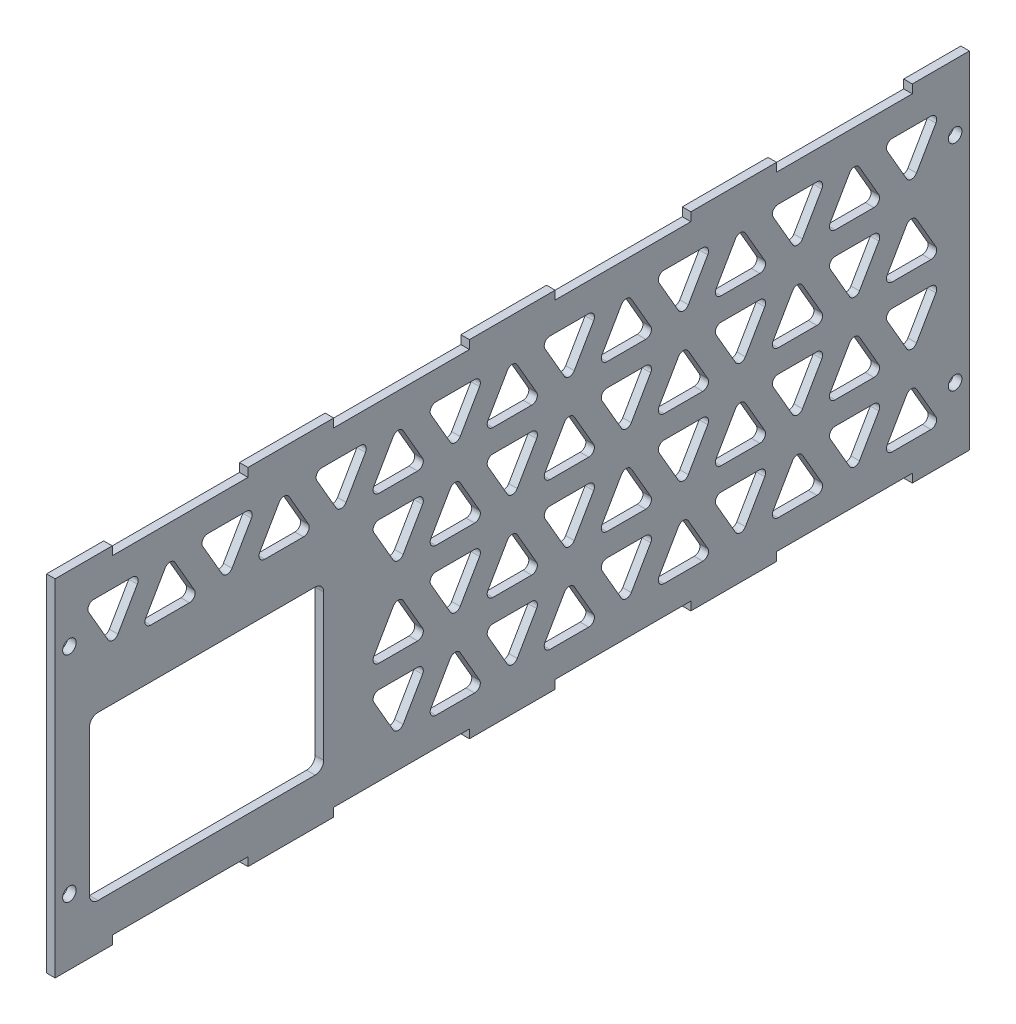
SolidWorks part; units mm, degrees
ref_plane "Front Plane" through (0, 0, 0) normal (0, 0, 1) x (1, 0, 0)
ref_plane "Top Plane" through (0, 0, 0) normal (0, 1, 0) x (1, 0, 0)
ref_plane "Right Plane" through (0, 0, 0) normal (1, 0, 0) x (0, 0, -1)
sketch "Sketch1" plane through (0, 0, 0) normal (1, 0, 0) x (0, 0, -1)
  line L1 (-160, -57.5) -> (160, -57.5)
  line L2 (-160, -57.5) -> (-160, 57.5)
  line L3 (-160, 57.5) -> (160, 57.5)
  line L4 (160, -57.5) -> (160, 57.5)
  line L5 (-160, -57.5) -> (160, 57.5) construction
  line L6 (-160, 57.5) -> (160, -57.5) construction
  point P0 (0, 0)
  dimension "D1" = 320
  dimension "D2" = 115
extrude "Boss-Extrude1" add sketch "Sketch1" along normal mid plane 3
sketch "Sketch2" plane through (1.5, 0, 0) normal (1, 0, 0) x (0, 0, -1)
  line L0 (160, 57.5) -> (-160, 57.5) construction
  line L1 (-160, 57.5) -> (-140, 57.5)
  line L2 (-160, 57.5) -> (-160, 60.5)
  line L3 (-160, 60.5) -> (-140, 60.5)
  line L4 (-140, 57.5) -> (-140, 60.5)
  line L5 (-92.5, 57.5) -> (-62.5, 57.5)
  line L6 (-92.5, 57.5) -> (-92.5, 60.5)
  line L7 (-92.5, 60.5) -> (-62.5, 60.5)
  line L8 (-62.5, 57.5) -> (-62.5, 60.5)
  line L9 (-15, 57.5) -> (-15, 60.5)
  line L10 (-15, 57.5) -> (15, 57.5)
  line L11 (15, 57.5) -> (15, 60.5)
  line L12 (-15, 60.5) -> (15, 60.5)
  line L13 (62.5, 57.5) -> (62.5, 60.5)
  line L14 (62.5, 57.5) -> (92.5, 57.5)
  line L15 (92.5, 57.5) -> (92.5, 60.5)
  line L16 (62.5, 60.5) -> (92.5, 60.5)
  line L17 (0, 57.5) -> (0, -57.5) construction
  line L18 (-160, -57.5) -> (160, -57.5) construction
  line L19 (140, 57.5) -> (140, 60.5)
  line L20 (160, 60.5) -> (140, 60.5)
  line L21 (160, 57.5) -> (160, 60.5)
  line L22 (160, 57.5) -> (140, 57.5)
  point P11 (-140, 59)
  dimension "D1" = 3
  dimension "D2" = 20
  dimension "D3" = 30
  dimension "D4" = 47.5
  dimension "D6" = 47.5
  dimension "D5" = 3
extrude "Boss-Extrude2" add sketch "Sketch2" along direction (-1, 0, 0) on the side against the normal up to surface (3 mm away) up to face at (-1.5, 0, 0)
mirror "Mirror1" about plane through (0, 0, 0) normal (0, 1, 0) of "Boss-Extrude2"
sketch "Sketch3" plane through (1.5, 0, 0) normal (1, 0, 0) x (0, 0, -1)
  line L1 (-148, -44.5) -> (-66, -44.5)
  line L2 (-148, -44.5) -> (-148, 12.5)
  line L3 (-148, 12.5) -> (-66, 12.5)
  line L4 (-66, -44.5) -> (-66, 12.5)
  line L5 (92.5, -57.5) -> (140, -57.5) construction
  line L7 (-160, 60.5) -> (-160, -60.5) construction
  dimension "D1" = 82
  dimension "D2" = 12
  dimension "D3" = 13
  dimension "D4" = 70
extrude "Cut-Extrude2" cut sketch "Sketch3" against normal through all
fillet "Fillet1" radius 3 4 edges at (0, 12.5, 66) (0, -44.5, 66) (0, -44.5, 148) (0, 12.5, 148)
sketch "Sketch4" plane through (-1.5, 0, 0) normal (-1, 0, 0) x (0, 0, 1)
  line L0 (1.65, 0) -> (-1.65, 0) construction
  line L1 (0, -1.65) -> (0, 1.65) construction
  circle A0 centre (155, -37.5) radius 2.375
  circle A2 centre (155, -37.5) radius 2.5 construction
  circle A3 centre (155, 37.5) radius 2.375
  circle A4 centre (-155, -37.5) radius 2.375
  circle A5 centre (-155, 37.5) radius 2.375
  point P2 (0, 0)
  dimension "D1" = 4.75
extrude "Cut-Extrude3" cut sketch "Sketch4" against normal up to next
sketch "Sketch5" plane through (1.5, 0, 0) normal (1, 0, 0) x (0, 0, -1)
  line L0 (129.5041, 47.5) -> (150, 47.5)
  line L1 (150, 47.5) -> (139.752, 29.75)
  line L2 (139.752, 29.75) -> (129.5041, 47.5)
  line L3 (119.7875, 47.5) -> (130.0354, 29.75)
  line L4 (130.0354, 29.75) -> (109.5395, 29.75)
  line L5 (109.5395, 29.75) -> (119.7875, 47.5)
  line L24 (140, 57.5) -> (92.5, 57.5) construction
  line L25 (160, -60.5) -> (160, 60.5) construction
  line L26 (109.5395, 25.75) -> (150, 25.75) construction
  line L27 (160, 0) -> (-160, 0) construction
  line L28 (-160, 60.5) -> (-160, -60.5) construction
  line L29 (109.5395, 21.75) -> (119.7875, 4)
  line L30 (130.0354, 21.75) -> (109.5395, 21.75)
  line L31 (119.7875, 4) -> (130.0354, 21.75)
  line L32 (139.752, 21.75) -> (129.5041, 4)
  line L33 (150, 4) -> (139.752, 21.75)
  line L34 (129.5041, 4) -> (150, 4)
  line L35 (129.5041, 47.5) -> (150, 47.5)
  line L36 (150, 47.5) -> (139.752, 29.75)
  line L37 (139.752, 29.75) -> (129.5041, 47.5)
  line L38 (119.7875, 47.5) -> (130.0354, 29.75)
  line L39 (130.0354, 29.75) -> (109.5395, 29.75)
  line L40 (109.5395, 29.75) -> (119.7875, 47.5)
  line L41 (109.5395, 21.75) -> (119.7875, 4)
  line L42 (130.0354, 21.75) -> (109.5395, 21.75)
  line L43 (119.7875, 4) -> (130.0354, 21.75)
  line L44 (139.752, 21.75) -> (129.5041, 4)
  line L45 (150, 4) -> (139.752, 21.75)
  line L46 (129.5041, 4) -> (150, 4)
  line L47 (109.5395, -25.75) -> (150, -25.75) construction
  line L48 (129.5041, -4) -> (150, -4)
  line L49 (150, -4) -> (139.752, -21.75)
  line L50 (139.752, -21.75) -> (129.5041, -4)
  line L51 (119.7875, -4) -> (130.0354, -21.75)
  line L52 (130.0354, -21.75) -> (109.5395, -21.75)
  line L53 (109.5395, -21.75) -> (119.7875, -4)
  line L54 (109.5395, -29.75) -> (119.7875, -47.5)
  line L55 (130.0354, -29.75) -> (109.5395, -29.75)
  line L56 (119.7875, -47.5) -> (130.0354, -29.75)
  line L57 (139.752, -29.75) -> (129.5041, -47.5)
  line L58 (150, -47.5) -> (139.752, -29.75)
  line L59 (129.5041, -47.5) -> (150, -47.5)
  line L60 (129.5041, -4) -> (150, -4)
  line L61 (150, -4) -> (139.752, -21.75)
  line L62 (139.752, -21.75) -> (129.5041, -4)
  line L63 (119.7875, -4) -> (130.0354, -21.75)
  line L64 (130.0354, -21.75) -> (109.5395, -21.75)
  line L65 (109.5395, -21.75) -> (119.7875, -4)
  line L66 (109.5395, -29.75) -> (119.7875, -47.5)
  line L67 (130.0354, -29.75) -> (109.5395, -29.75)
  line L68 (119.7875, -47.5) -> (130.0354, -29.75)
  line L69 (139.752, -29.75) -> (129.5041, -47.5)
  line L70 (150, -47.5) -> (139.752, -29.75)
  line L71 (129.5041, -47.5) -> (150, -47.5)
  line L72 (89.5749, 47.5) -> (110.0708, 47.5)
  line L73 (110.0708, 47.5) -> (99.8229, 29.75)
  line L74 (99.8229, 29.75) -> (89.5749, 47.5)
  line L75 (79.8583, 47.5) -> (90.1063, 29.75)
  line L76 (90.1063, 29.75) -> (69.6103, 29.75)
  line L77 (69.6103, 29.75) -> (79.8583, 47.5)
  line L78 (69.6103, 21.75) -> (79.8583, 4)
  line L79 (90.1063, 21.75) -> (69.6103, 21.75)
  line L80 (79.8583, 4) -> (90.1063, 21.75)
  line L81 (99.8229, 21.75) -> (89.5749, 4)
  line L82 (110.0708, 4) -> (99.8229, 21.75)
  line L83 (89.5749, 4) -> (110.0708, 4)
  line L84 (89.5749, 47.5) -> (110.0708, 47.5)
  line L85 (110.0708, 47.5) -> (99.8229, 29.75)
  line L86 (99.8229, 29.75) -> (89.5749, 47.5)
  line L87 (79.8583, 47.5) -> (90.1063, 29.75)
  line L88 (90.1063, 29.75) -> (69.6103, 29.75)
  line L89 (69.6103, 29.75) -> (79.8583, 47.5)
  line L90 (69.6103, 21.75) -> (79.8583, 4)
  line L91 (90.1063, 21.75) -> (69.6103, 21.75)
  line L92 (79.8583, 4) -> (90.1063, 21.75)
  line L93 (99.8229, 21.75) -> (89.5749, 4)
  line L94 (110.0708, 4) -> (99.8229, 21.75)
  line L95 (89.5749, 4) -> (110.0708, 4)
  line L96 (89.5749, -4) -> (110.0708, -4)
  line L97 (110.0708, -4) -> (99.8229, -21.75)
  line L98 (99.8229, -21.75) -> (89.5749, -4)
  line L99 (79.8583, -4) -> (90.1063, -21.75)
  line L100 (90.1063, -21.75) -> (69.6103, -21.75)
  line L101 (69.6103, -21.75) -> (79.8583, -4)
  line L102 (69.6103, -29.75) -> (79.8583, -47.5)
  line L103 (90.1063, -29.75) -> (69.6103, -29.75)
  line L104 (79.8583, -47.5) -> (90.1063, -29.75)
  line L105 (99.8229, -29.75) -> (89.5749, -47.5)
  line L106 (110.0708, -47.5) -> (99.8229, -29.75)
  line L107 (89.5749, -47.5) -> (110.0708, -47.5)
  line L108 (89.5749, -4) -> (110.0708, -4)
  line L109 (110.0708, -4) -> (99.8229, -21.75)
  line L110 (99.8229, -21.75) -> (89.5749, -4)
  line L111 (79.8583, -4) -> (90.1063, -21.75)
  line L112 (90.1063, -21.75) -> (69.6103, -21.75)
  line L113 (69.6103, -21.75) -> (79.8583, -4)
  line L114 (69.6103, -29.75) -> (79.8583, -47.5)
  line L115 (90.1063, -29.75) -> (69.6103, -29.75)
  line L116 (79.8583, -47.5) -> (90.1063, -29.75)
  line L117 (99.8229, -29.75) -> (89.5749, -47.5)
  line L118 (110.0708, -47.5) -> (99.8229, -29.75)
  line L119 (89.5749, -47.5) -> (110.0708, -47.5)
  line L120 (110.0708, 47.5) -> (119.7875, 47.5) construction
  line L121 (129.5041, 47.5) -> (119.7875, 47.5) construction
  line L122 (49.6458, 47.5) -> (70.1417, 47.5)
  line L123 (70.1417, 47.5) -> (59.8937, 29.75)
  line L124 (59.8937, 29.75) -> (49.6458, 47.5)
  line L125 (39.9292, 47.5) -> (50.1771, 29.75)
  line L126 (50.1771, 29.75) -> (29.6812, 29.75)
  line L127 (29.6812, 29.75) -> (39.9292, 47.5)
  line L128 (29.6812, 21.75) -> (39.9292, 4)
  line L129 (50.1771, 21.75) -> (29.6812, 21.75)
  line L130 (39.9292, 4) -> (50.1771, 21.75)
  line L131 (59.8937, 21.75) -> (49.6458, 4)
  line L132 (70.1417, 4) -> (59.8937, 21.75)
  line L133 (49.6458, 4) -> (70.1417, 4)
  line L134 (49.6458, 47.5) -> (70.1417, 47.5)
  line L135 (70.1417, 47.5) -> (59.8937, 29.75)
  line L136 (59.8937, 29.75) -> (49.6458, 47.5)
  line L137 (39.9292, 47.5) -> (50.1771, 29.75)
  line L138 (50.1771, 29.75) -> (29.6812, 29.75)
  line L139 (29.6812, 29.75) -> (39.9292, 47.5)
  line L140 (29.6812, 21.75) -> (39.9292, 4)
  line L141 (50.1771, 21.75) -> (29.6812, 21.75)
  line L142 (39.9292, 4) -> (50.1771, 21.75)
  line L143 (59.8937, 21.75) -> (49.6458, 4)
  line L144 (70.1417, 4) -> (59.8937, 21.75)
  line L145 (49.6458, 4) -> (70.1417, 4)
  line L146 (49.6458, -4) -> (70.1417, -4)
  line L147 (70.1417, -4) -> (59.8937, -21.75)
  line L148 (59.8937, -21.75) -> (49.6458, -4)
  line L149 (39.9292, -4) -> (50.1771, -21.75)
  line L150 (50.1771, -21.75) -> (29.6812, -21.75)
  line L151 (29.6812, -21.75) -> (39.9292, -4)
  line L152 (29.6812, -29.75) -> (39.9292, -47.5)
  line L153 (50.1771, -29.75) -> (29.6812, -29.75)
  line L154 (39.9292, -47.5) -> (50.1771, -29.75)
  line L155 (59.8937, -29.75) -> (49.6458, -47.5)
  line L156 (70.1417, -47.5) -> (59.8937, -29.75)
  line L157 (49.6458, -47.5) -> (70.1417, -47.5)
  line L158 (49.6458, -4) -> (70.1417, -4)
  line L159 (70.1417, -4) -> (59.8937, -21.75)
  line L160 (59.8937, -21.75) -> (49.6458, -4)
  line L161 (39.9292, -4) -> (50.1771, -21.75)
  line L162 (50.1771, -21.75) -> (29.6812, -21.75)
  line L163 (29.6812, -21.75) -> (39.9292, -4)
  line L164 (29.6812, -29.75) -> (39.9292, -47.5)
  line L165 (50.1771, -29.75) -> (29.6812, -29.75)
  line L166 (39.9292, -47.5) -> (50.1771, -29.75)
  line L167 (59.8937, -29.75) -> (49.6458, -47.5)
  line L168 (70.1417, -47.5) -> (59.8937, -29.75)
  line L169 (49.6458, -47.5) -> (70.1417, -47.5)
  line L172 (9.7166, 47.5) -> (30.2125, 47.5)
  line L173 (30.2125, 47.5) -> (19.9646, 29.75)
  line L174 (19.9646, 29.75) -> (9.7166, 47.5)
  line L175 (0, 47.5) -> (10.248, 29.75)
  line L176 (10.248, 29.75) -> (-10.248, 29.75)
  line L177 (-10.248, 29.75) -> (0, 47.5)
  line L178 (-10.248, 21.75) -> (0, 4)
  line L179 (10.248, 21.75) -> (-10.248, 21.75)
  line L180 (0, 4) -> (10.248, 21.75)
  line L181 (19.9646, 21.75) -> (9.7166, 4)
  line L182 (30.2125, 4) -> (19.9646, 21.75)
  line L183 (9.7166, 4) -> (30.2125, 4)
  line L184 (9.7166, 47.5) -> (30.2125, 47.5)
  line L185 (30.2125, 47.5) -> (19.9646, 29.75)
  line L186 (19.9646, 29.75) -> (9.7166, 47.5)
  line L187 (0, 47.5) -> (10.248, 29.75)
  line L188 (10.248, 29.75) -> (-10.248, 29.75)
  line L189 (-10.248, 29.75) -> (0, 47.5)
  line L190 (-10.248, 21.75) -> (0, 4)
  line L191 (10.248, 21.75) -> (-10.248, 21.75)
  line L192 (0, 4) -> (10.248, 21.75)
  line L193 (19.9646, 21.75) -> (9.7166, 4)
  line L194 (30.2125, 4) -> (19.9646, 21.75)
  line L195 (9.7166, 4) -> (30.2125, 4)
  line L196 (9.7166, -4) -> (30.2125, -4)
  line L197 (30.2125, -4) -> (19.9646, -21.75)
  line L198 (19.9646, -21.75) -> (9.7166, -4)
  line L199 (0, -4) -> (10.248, -21.75)
  line L200 (10.248, -21.75) -> (-10.248, -21.75)
  line L201 (-10.248, -21.75) -> (0, -4)
  line L202 (-10.248, -29.75) -> (0, -47.5)
  line L203 (10.248, -29.75) -> (-10.248, -29.75)
  line L204 (0, -47.5) -> (10.248, -29.75)
  line L205 (19.9646, -29.75) -> (9.7166, -47.5)
  line L206 (30.2125, -47.5) -> (19.9646, -29.75)
  line L207 (9.7166, -47.5) -> (30.2125, -47.5)
  line L208 (9.7166, -4) -> (30.2125, -4)
  line L209 (30.2125, -4) -> (19.9646, -21.75)
  line L210 (19.9646, -21.75) -> (9.7166, -4)
  line L211 (0, -4) -> (10.248, -21.75)
  line L212 (10.248, -21.75) -> (-10.248, -21.75)
  line L213 (-10.248, -21.75) -> (0, -4)
  line L214 (-10.248, -29.75) -> (0, -47.5)
  line L215 (10.248, -29.75) -> (-10.248, -29.75)
  line L216 (0, -47.5) -> (10.248, -29.75)
  line L217 (19.9646, -29.75) -> (9.7166, -47.5)
  line L218 (30.2125, -47.5) -> (19.9646, -29.75)
  line L219 (9.7166, -47.5) -> (30.2125, -47.5)
  line L221 (-56, -41.5) -> (-56, 9.5)
  line L222 (-30.2125, 47.5) -> (-9.7166, 47.5)
  line L223 (-9.7166, 47.5) -> (-19.9646, 29.75)
  line L224 (-19.9646, 29.75) -> (-30.2125, 47.5)
  line L225 (-39.9292, 47.5) -> (-29.6812, 29.75)
  line L226 (-29.6812, 29.75) -> (-50.1771, 29.75)
  line L227 (-50.1771, 29.75) -> (-39.9292, 47.5)
  line L228 (-50.1771, 21.75) -> (-39.9292, 4)
  line L229 (-29.6812, 21.75) -> (-50.1771, 21.75)
  line L230 (-39.9292, 4) -> (-29.6812, 21.75)
  line L231 (-19.9646, 21.75) -> (-30.2125, 4)
  line L232 (-9.7166, 4) -> (-19.9646, 21.75)
  line L233 (-30.2125, 4) -> (-9.7166, 4)
  line L234 (-30.2125, 47.5) -> (-9.7166, 47.5)
  line L235 (-9.7166, 47.5) -> (-19.9646, 29.75)
  line L236 (-19.9646, 29.75) -> (-30.2125, 47.5)
  line L237 (-39.9292, 47.5) -> (-29.6812, 29.75)
  line L238 (-29.6812, 29.75) -> (-50.1771, 29.75)
  line L239 (-50.1771, 29.75) -> (-39.9292, 47.5)
  line L240 (-50.1771, 21.75) -> (-39.9292, 4)
  line L241 (-29.6812, 21.75) -> (-50.1771, 21.75)
  line L242 (-39.9292, 4) -> (-29.6812, 21.75)
  line L243 (-19.9646, 21.75) -> (-30.2125, 4)
  line L244 (-9.7166, 4) -> (-19.9646, 21.75)
  line L245 (-30.2125, 4) -> (-9.7166, 4)
  line L246 (-30.2125, -4) -> (-9.7166, -4)
  line L247 (-9.7166, -4) -> (-19.9646, -21.75)
  line L248 (-19.9646, -21.75) -> (-30.2125, -4)
  line L249 (-39.9292, -4) -> (-29.6812, -21.75)
  line L250 (-29.6812, -21.75) -> (-50.1771, -21.75)
  line L251 (-50.1771, -21.75) -> (-39.9292, -4)
  line L252 (-50.1771, -29.75) -> (-39.9292, -47.5)
  line L253 (-29.6812, -29.75) -> (-50.1771, -29.75)
  line L254 (-39.9292, -47.5) -> (-29.6812, -29.75)
  line L255 (-19.9646, -29.75) -> (-30.2125, -47.5)
  line L256 (-9.7166, -47.5) -> (-19.9646, -29.75)
  line L257 (-30.2125, -47.5) -> (-9.7166, -47.5)
  line L258 (-30.2125, -4) -> (-9.7166, -4)
  line L259 (-9.7166, -4) -> (-19.9646, -21.75)
  line L260 (-19.9646, -21.75) -> (-30.2125, -4)
  line L261 (-39.9292, -4) -> (-29.6812, -21.75)
  line L262 (-29.6812, -21.75) -> (-50.1771, -21.75)
  line L263 (-50.1771, -21.75) -> (-39.9292, -4)
  line L264 (-50.1771, -29.75) -> (-39.9292, -47.5)
  line L265 (-29.6812, -29.75) -> (-50.1771, -29.75)
  line L266 (-39.9292, -47.5) -> (-29.6812, -29.75)
  line L267 (-19.9646, -29.75) -> (-30.2125, -47.5)
  line L268 (-9.7166, -47.5) -> (-19.9646, -29.75)
  line L269 (-30.2125, -47.5) -> (-9.7166, -47.5)
  line L270 (-69, 22.5) -> (-145, 22.5)
  line L271 (-56, -41.5) -> (-56, 9.5) construction
  line L272 (-70.1417, 47.5) -> (-49.6458, 47.5)
  line L273 (-49.6458, 47.5) -> (-59.8937, 29.75)
  line L274 (-59.8937, 29.75) -> (-70.1417, 47.5)
  line L275 (-79.8583, 47.5) -> (-69.6103, 29.75)
  line L276 (-69.6103, 29.75) -> (-90.1063, 29.75)
  line L277 (-90.1063, 29.75) -> (-79.8583, 47.5)
  line L284 (-70.1417, 47.5) -> (-49.6458, 47.5)
  line L285 (-49.6458, 47.5) -> (-59.8937, 29.75)
  line L286 (-59.8937, 29.75) -> (-70.1417, 47.5)
  line L287 (-79.8583, 47.5) -> (-69.6103, 29.75)
  line L288 (-69.6103, 29.75) -> (-90.1063, 29.75)
  line L289 (-90.1063, 29.75) -> (-79.8583, 47.5)
  line L320 (-69, 22.5) -> (-145, 22.5) construction
  line L322 (-110.0708, 47.5) -> (-89.5749, 47.5)
  line L323 (-89.5749, 47.5) -> (-99.8229, 29.75)
  line L324 (-99.8229, 29.75) -> (-110.0708, 47.5)
  line L325 (-119.7875, 47.5) -> (-109.5395, 29.75)
  line L326 (-109.5395, 29.75) -> (-130.0354, 29.75)
  line L327 (-130.0354, 29.75) -> (-119.7875, 47.5)
  line L334 (-110.0708, 47.5) -> (-89.5749, 47.5)
  line L335 (-89.5749, 47.5) -> (-99.8229, 29.75)
  line L336 (-99.8229, 29.75) -> (-110.0708, 47.5)
  line L337 (-119.7875, 47.5) -> (-109.5395, 29.75)
  line L338 (-109.5395, 29.75) -> (-130.0354, 29.75)
  line L339 (-130.0354, 29.75) -> (-119.7875, 47.5)
  line L372 (-150, 47.5) -> (-129.5041, 47.5)
  line L373 (-129.5041, 47.5) -> (-139.752, 29.75)
  line L374 (-139.752, 29.75) -> (-150, 47.5)
  line L384 (-150, 47.5) -> (-129.5041, 47.5)
  line L385 (-129.5041, 47.5) -> (-139.752, 29.75)
  line L386 (-139.752, 29.75) -> (-150, 47.5)
  line L422 (150, 47.5) -> (160, 47.5) construction
  line L423 (-150, 47.5) -> (-160, 47.5) construction
  line L425 (-159.7166, 47.5) -> (-149.4686, 29.75) [skipped]
  line L426 (-149.4686, 29.75) -> (-169.9646, 29.75) [skipped]
  line L427 (-169.9646, 29.75) -> (-159.7166, 47.5) [skipped]
  line L428 (-169.9646, 21.75) -> (-159.7166, 4) [skipped]
  line L429 (-149.4686, 21.75) -> (-169.9646, 21.75) [skipped]
  line L430 (-159.7166, 4) -> (-149.4686, 21.75) [skipped]
  line L431 (-159.7166, 47.5) -> (-149.4686, 29.75) [skipped]
  line L432 (-149.4686, 29.75) -> (-169.9646, 29.75) [skipped]
  line L433 (-169.9646, 29.75) -> (-159.7166, 47.5) [skipped]
  line L434 (-169.9646, 21.75) -> (-159.7166, 4) [skipped]
  line L435 (-149.4686, 21.75) -> (-169.9646, 21.75) [skipped]
  line L436 (-159.7166, 4) -> (-149.4686, 21.75) [skipped]
  line L437 (-159.7166, -4) -> (-149.4686, -21.75) [skipped]
  line L438 (-149.4686, -21.75) -> (-169.9646, -21.75) [skipped]
  line L439 (-169.9646, -21.75) -> (-159.7166, -4) [skipped]
  line L440 (-169.9646, -29.75) -> (-159.7166, -47.5) [skipped]
  line L441 (-149.4686, -29.75) -> (-169.9646, -29.75) [skipped]
  line L442 (-159.7166, -47.5) -> (-149.4686, -29.75) [skipped]
  line L443 (-159.7166, -4) -> (-149.4686, -21.75) [skipped]
  line L444 (-149.4686, -21.75) -> (-169.9646, -21.75) [skipped]
  line L445 (-169.9646, -21.75) -> (-159.7166, -4) [skipped]
  line L446 (-169.9646, -29.75) -> (-159.7166, -47.5) [skipped]
  line L447 (-149.4686, -29.75) -> (-169.9646, -29.75) [skipped]
  line L448 (-159.7166, -47.5) -> (-149.4686, -29.75) [skipped]
  line L449 (-169.9646, 25.75) -> (-129.5041, 25.75) construction
  line L450 (-130.0354, 25.75) -> (-89.5749, 25.75) construction
  line L451 (-90.1063, 25.75) -> (-49.6458, 25.75) construction
  line L452 (-50.1771, 25.75) -> (-9.7166, 25.75) construction
  line L453 (-10.248, 25.75) -> (30.2125, 25.75) construction
  line L454 (29.6812, 25.75) -> (70.1417, 25.75) construction
  line L455 (69.6103, 25.75) -> (110.0708, 25.75) construction
  line L456 (69.6103, -25.75) -> (110.0708, -25.75) construction
  line L457 (29.6812, -25.75) -> (70.1417, -25.75) construction
  line L458 (-10.248, -25.75) -> (30.2125, -25.75) construction
  line L459 (-50.1771, -25.75) -> (-9.7166, -25.75) construction
  line L460 (-90.1063, -25.75) -> (-49.6458, -25.75) construction
  line L461 (-130.0354, -25.75) -> (-89.5749, -25.75) construction
  line L462 (-169.9646, -25.75) -> (-129.5041, -25.75) construction
  line L463 (-90.1063, 21.75) -> (-79.8583, 4) [skipped]
  line L464 (-69.6103, 21.75) -> (-90.1063, 21.75) [skipped]
  line L465 (-79.8583, 4) -> (-69.6103, 21.75) [skipped]
  line L466 (-59.8937, 21.75) -> (-70.1417, 4) [skipped]
  line L467 (-49.6458, 4) -> (-59.8937, 21.75) [skipped]
  line L468 (-70.1417, 4) -> (-49.6458, 4) [skipped]
  line L469 (-90.1063, 21.75) -> (-79.8583, 4) [skipped]
  line L470 (-69.6103, 21.75) -> (-90.1063, 21.75) [skipped]
  line L471 (-79.8583, 4) -> (-69.6103, 21.75) [skipped]
  line L472 (-59.8937, 21.75) -> (-70.1417, 4) [skipped]
  line L473 (-49.6458, 4) -> (-59.8937, 21.75) [skipped]
  line L474 (-70.1417, 4) -> (-49.6458, 4) [skipped]
  line L475 (-70.1417, -4) -> (-49.6458, -4) [skipped]
  line L476 (-49.6458, -4) -> (-59.8937, -21.75) [skipped]
  line L477 (-59.8937, -21.75) -> (-70.1417, -4) [skipped]
  line L478 (-79.8583, -4) -> (-69.6103, -21.75) [skipped]
  line L479 (-69.6103, -21.75) -> (-90.1063, -21.75) [skipped]
  line L480 (-90.1063, -21.75) -> (-79.8583, -4) [skipped]
  line L481 (-90.1063, -29.75) -> (-79.8583, -47.5) [skipped]
  line L482 (-69.6103, -29.75) -> (-90.1063, -29.75) [skipped]
  line L483 (-79.8583, -47.5) -> (-69.6103, -29.75) [skipped]
  line L484 (-59.8937, -29.75) -> (-70.1417, -47.5) [skipped]
  line L485 (-49.6458, -47.5) -> (-59.8937, -29.75) [skipped]
  line L486 (-70.1417, -47.5) -> (-49.6458, -47.5) [skipped]
  line L487 (-70.1417, -4) -> (-49.6458, -4) [skipped]
  line L488 (-49.6458, -4) -> (-59.8937, -21.75) [skipped]
  line L489 (-59.8937, -21.75) -> (-70.1417, -4) [skipped]
  line L490 (-79.8583, -4) -> (-69.6103, -21.75) [skipped]
  line L491 (-69.6103, -21.75) -> (-90.1063, -21.75) [skipped]
  line L492 (-90.1063, -21.75) -> (-79.8583, -4) [skipped]
  line L493 (-90.1063, -29.75) -> (-79.8583, -47.5) [skipped]
  line L494 (-69.6103, -29.75) -> (-90.1063, -29.75) [skipped]
  line L495 (-79.8583, -47.5) -> (-69.6103, -29.75) [skipped]
  line L496 (-59.8937, -29.75) -> (-70.1417, -47.5) [skipped]
  line L497 (-49.6458, -47.5) -> (-59.8937, -29.75) [skipped]
  line L498 (-70.1417, -47.5) -> (-49.6458, -47.5) [skipped]
  line L499 (-130.0354, 21.75) -> (-119.7875, 4) [skipped]
  line L500 (-109.5395, 21.75) -> (-130.0354, 21.75) [skipped]
  line L501 (-119.7875, 4) -> (-109.5395, 21.75) [skipped]
  line L502 (-99.8229, 21.75) -> (-110.0708, 4) [skipped]
  line L503 (-89.5749, 4) -> (-99.8229, 21.75) [skipped]
  line L504 (-110.0708, 4) -> (-89.5749, 4) [skipped]
  line L505 (-130.0354, 21.75) -> (-119.7875, 4) [skipped]
  line L506 (-109.5395, 21.75) -> (-130.0354, 21.75) [skipped]
  line L507 (-119.7875, 4) -> (-109.5395, 21.75) [skipped]
  line L508 (-99.8229, 21.75) -> (-110.0708, 4) [skipped]
  line L509 (-89.5749, 4) -> (-99.8229, 21.75) [skipped]
  line L510 (-110.0708, 4) -> (-89.5749, 4) [skipped]
  line L511 (-110.0708, -4) -> (-89.5749, -4) [skipped]
  line L512 (-89.5749, -4) -> (-99.8229, -21.75) [skipped]
  line L513 (-99.8229, -21.75) -> (-110.0708, -4) [skipped]
  line L514 (-119.7875, -4) -> (-109.5395, -21.75) [skipped]
  line L515 (-109.5395, -21.75) -> (-130.0354, -21.75) [skipped]
  line L516 (-130.0354, -21.75) -> (-119.7875, -4) [skipped]
  line L517 (-130.0354, -29.75) -> (-119.7875, -47.5) [skipped]
  line L518 (-109.5395, -29.75) -> (-130.0354, -29.75) [skipped]
  line L519 (-119.7875, -47.5) -> (-109.5395, -29.75) [skipped]
  line L520 (-99.8229, -29.75) -> (-110.0708, -47.5) [skipped]
  line L521 (-89.5749, -47.5) -> (-99.8229, -29.75) [skipped]
  line L522 (-110.0708, -47.5) -> (-89.5749, -47.5) [skipped]
  line L523 (-110.0708, -4) -> (-89.5749, -4) [skipped]
  line L524 (-89.5749, -4) -> (-99.8229, -21.75) [skipped]
  line L525 (-99.8229, -21.75) -> (-110.0708, -4) [skipped]
  line L526 (-119.7875, -4) -> (-109.5395, -21.75) [skipped]
  line L527 (-109.5395, -21.75) -> (-130.0354, -21.75) [skipped]
  line L528 (-130.0354, -21.75) -> (-119.7875, -4) [skipped]
  line L529 (-130.0354, -29.75) -> (-119.7875, -47.5) [skipped]
  line L530 (-109.5395, -29.75) -> (-130.0354, -29.75) [skipped]
  line L531 (-119.7875, -47.5) -> (-109.5395, -29.75) [skipped]
  line L532 (-99.8229, -29.75) -> (-110.0708, -47.5) [skipped]
  line L533 (-89.5749, -47.5) -> (-99.8229, -29.75) [skipped]
  line L534 (-110.0708, -47.5) -> (-89.5749, -47.5) [skipped]
  line L535 (-139.752, 21.75) -> (-150, 4) [skipped]
  line L536 (-129.5041, 4) -> (-139.752, 21.75) [skipped]
  line L537 (-150, 4) -> (-129.5041, 4) [skipped]
  line L538 (-139.752, 21.75) -> (-150, 4) [skipped]
  line L539 (-129.5041, 4) -> (-139.752, 21.75) [skipped]
  line L540 (-150, 4) -> (-129.5041, 4) [skipped]
  line L541 (-150, -4) -> (-129.5041, -4) [skipped]
  line L542 (-129.5041, -4) -> (-139.752, -21.75) [skipped]
  line L543 (-139.752, -21.75) -> (-150, -4) [skipped]
  line L544 (-139.752, -29.75) -> (-150, -47.5) [skipped]
  line L545 (-129.5041, -47.5) -> (-139.752, -29.75) [skipped]
  line L546 (-150, -47.5) -> (-129.5041, -47.5) [skipped]
  line L547 (-150, -4) -> (-129.5041, -4) [skipped]
  line L548 (-129.5041, -4) -> (-139.752, -21.75) [skipped]
  line L549 (-139.752, -21.75) -> (-150, -4) [skipped]
  line L550 (-139.752, -29.75) -> (-150, -47.5) [skipped]
  line L551 (-129.5041, -47.5) -> (-139.752, -29.75) [skipped]
  line L552 (-150, -47.5) -> (-129.5041, -47.5) [skipped]
  arc A4 (-56, 9.5) -> (-69, 22.5) centre (-69, 9.5) ccw
  arc A5 (-56, 9.5) -> (-69, 22.5) centre (-69, 9.5) ccw construction
  dimension "D1" = 10
  dimension "D2" = 10
  dimension "D4" = 4
  dimension "D5" = 4
  dimension "D7" = 10
  dimension "D6" = 8
extrude "Cut-Extrude4" cut sketch "Sketch5" against normal up to next (3 mm away) contours L374 L373 L372 | L327 L326 L325 | L324 L323 L322 | L277 L276 L275 | L274 L273 L272 | L227 L226 L225 | L224 L223 L222 | L177 L176 L175 | L174 L173 L172 | L127 L126 L125 | L124 L123 L122 | L77 L76 L75 | L74 L73 L72 | L5 L4 L3 | L2 L1 L0 | L32 L34 L33 | L50 L49 L48 | L57 L59 L58 | L54 L56 L55 | L53 L52 L51 | L29 L31 L30 | L81 L83 L82 | L98 L97 L96 | L105 L107 L106 | L102 L104 L103 | L101 L100 L99 | L78 L80 L79 | L131 L133 L132 | L148 L147 L146 | L155 L157 L156 | L152 L154 L153 | L151 L150 L149 | L128 L130 L129 | L181 L183 L182 | L198 L197 L196 | L205 L207 L206 | L202 L204 L203 | L201 L200 L199 | L178 L180 L179 | L231 L233 L232 | L228 L230 L229 | L251 L250 L249 | L248 L247 L246 | L255 L257 L256 | L252 L254 L253 region at (1.5, 41.5833, -139.752) region at (1.5, 35.6667, -119.7875) region at (1.5, 15.8333, -119.7875) region at (1.5, 9.9167, -139.752) region at (1.5, -9.9167, -139.752) region at (1.5, -15.8333, -119.7875) region at (1.5, -35.6667, -119.7875) region at (1.5, -41.5833, -139.752) region at (1.5, 41.5833, -99.8229) region at (1.5, 35.6667, -79.8583) region at (1.5, 15.8333, -79.8583) region at (1.5, 9.9167, -99.8229) region at (1.5, -9.9167, -99.8229) region at (1.5, -15.8333, -79.8583) region at (1.5, -35.6667, -79.8583) region at (1.5, -41.5833, -99.8229) region at (1.5, 41.5833, -59.8937) region at (1.5, 35.6667, -39.9292) region at (1.5, 15.8333, -39.9292) region at (1.5, 9.9167, -59.8937) region at (1.5, -9.9167, -59.8937) region at (1.5, -15.8333, -39.9292) region at (1.5, -35.6667, -39.9292) region at (1.5, -41.5833, -59.8937) region at (1.5, 41.5833, -19.9646) region at (1.5, 35.6667, 0) region at (1.5, 15.8333, 0) region at (1.5, 9.9167, -19.9646) region at (1.5, -9.9167, -19.9646) region at (1.5, -15.8333, 0) region at (1.5, -35.6667, 0) region at (1.5, -41.5833, -19.9646) region at (1.5, 41.5833, 19.9646) region at (1.5, 35.6667, 39.9292) region at (1.5, 15.8333, 39.9292) region at (1.5, 9.9167, 19.9646) region at (1.5, -9.9167, 19.9646) region at (1.5, -15.8333, 39.9292) region at (1.5, -35.6667, 39.9292) region at (1.5, -41.5833, 19.9646) region at (1.5, 41.5833, 59.8937) region at (1.5, 35.6667, 79.8583) region at (1.5, 41.5833, 99.8229) region at (1.5, 35.6667, 119.7875) region at (1.5, 41.5833, 139.752)
fillet "Fillet2" radius 2 135 edges at (0, 47.5, 129.5041) (0, 29.75, 139.752) (0, 47.5, 150) (0, -21.75, -10.248) (0, -21.75, 10.248) (0, -4, 0) (0, -4, -30.2125) (0, -21.75, -19.9646) (0, -4, -9.7166) (0, -21.75, 29.6812) (0, -21.75, 50.1771) (0, -4, 39.9292) (0, -4, 9.7166) (0, -21.75, 19.9646) (0, -4, 30.2125) (0, 29.75, 109.5395) (0, 29.75, 130.0354) (0, 47.5, 119.7875) (0, 47.5, 89.5749) (0, 29.75, 99.8229) (0, 47.5, 110.0708) (0, 29.75, 69.6103) (0, 29.75, 90.1063) (0, 47.5, 79.8583) (0, 47.5, 49.6458) (0, 29.75, 59.8937) (0, 47.5, 70.1417) (0, 29.75, 29.6812) (0, 29.75, 50.1771) (0, 47.5, 39.9292) (0, 47.5, 9.7166) (0, 29.75, 19.9646) (0, 47.5, 30.2125) (0, 29.75, -10.248) (0, 29.75, 10.248) (0, 47.5, 0) (0, 47.5, -30.2125) (0, 29.75, -19.9646) (0, 47.5, -9.7166) (0, 29.75, -50.1771) (0, 29.75, -29.6812) (0, 47.5, -39.9292) (0, 47.5, -70.1417) (0, 29.75, -59.8937) (0, 47.5, -49.6458) (0, 29.75, -90.1063) (0, 29.75, -69.6103) (0, 47.5, -79.8583) (0, 47.5, -110.0708) (0, 29.75, -99.8229) (0, 47.5, -89.5749) (0, 29.75, -130.0354) (0, 29.75, -109.5395) (0, 47.5, -119.7875) (0, 47.5, -150) (0, 29.75, -139.752) (0, 47.5, -129.5041) (0, -4, -150) (0, -21.75, -139.752) (0, -4, -129.5041) (0, -21.75, -90.1063) (0, -21.75, -69.6103) (0, -4, -79.8583) (0, -4, -70.1417) (0, -21.75, -59.8937) (0, -4, -49.6458) (0, -21.75, -50.1771) (0, -21.75, -29.6812) (0, -4, -39.9292) (0, -4, -110.0708) (0, -21.75, -99.8229) (0, -4, -89.5749) (0, -21.75, -130.0354) (0, -21.75, -109.5395) (0, -4, -119.7875) (0, -29.75, -139.752) (0, -47.5, -150) (0, -47.5, -129.5041) (0, -29.75, -109.5395) (0, -29.75, -130.0354) (0, -47.5, -119.7875) (0, 21.75, -109.5395) (0, 21.75, -130.0354) (0, 4, -119.7875) (0, 21.75, -99.8229) (0, 4, -110.0708) (0, 4, -89.5749) (0, -29.75, -99.8229) (0, -47.5, -110.0708) (0, -47.5, -89.5749) (0, -29.75, -69.6103) (0, -29.75, -90.1063) (0, -47.5, -79.8583) (0, 21.75, -29.6812) (0, 21.75, -50.1771) (0, 4, -39.9292) (0, -29.75, -29.6812) (0, -29.75, -50.1771) (0, -47.5, -39.9292) (0, -29.75, -59.8937) (0, -47.5, -70.1417) (0, -47.5, -49.6458) (0, 21.75, -59.8937) (0, 4, -70.1417) (0, 21.75, -69.6103) (0, 21.75, -90.1063) (0, 4, -79.8583) (0, 21.75, -139.752) (0, 4, -150) (0, 4, -129.5041) (0, -29.75, 50.1771) (0, -29.75, 29.6812) (0, -47.5, 39.9292) (0, -29.75, 19.9646) (0, -47.5, 9.7166) (0, -47.5, 30.2125) (0, 21.75, -19.9646) (0, 4, -30.2125) (0, 4, -9.7166) (0, -29.75, -19.9646) (0, -47.5, -30.2125) (0, -47.5, -9.7166) (0, -29.75, 10.248) (0, -29.75, -10.248) (0, -47.5, 0) (0, 21.75, 10.248) (0, 21.75, -10.248) (0, 4, 0) (0, 21.75, 19.9646) (0, 4, 9.7166) (0, 4, 30.2125) (0, 21.75, 50.1771) (0, 21.75, 29.6812) (0, 4, 39.9292) (0, 4, -49.6458)
